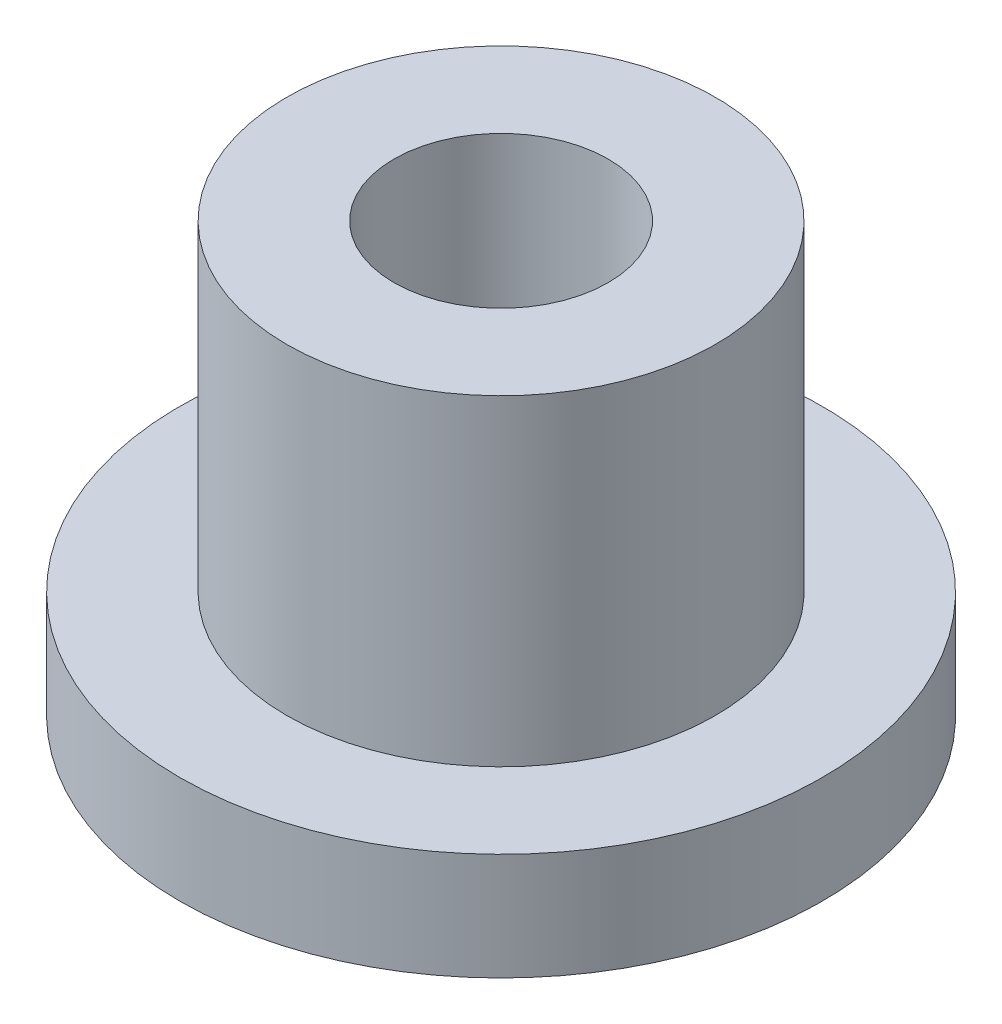
SolidWorks part; units mm, degrees
ref_plane "Front Plane" through (0, 0, 0) normal (0, 0, 1) x (1, 0, 0)
ref_plane "Top Plane" through (0, 0, 0) normal (0, 1, 0) x (1, 0, 0)
ref_plane "Right Plane" through (0, 0, 0) normal (1, 0, 0) x (0, 0, -1)
sketch "Sketch1" plane through (0, 0, 0) normal (0, 1, 0) x (1, 0, 0)
  circle A0 centre (0, 0) radius 6
  circle A1 centre (0, 0) radius 4
  circle A2 centre (0, 0) radius 2
  dimension "D1" = 12
  dimension "D2" = 8
  dimension "D3" = 4
extrude "Boss-Extrude1" add sketch "Sketch1" along normal blind 2 contours A0 A1 region at (-5.8303, 0, 0)
extrude "Boss-Extrude2" add sketch "Sketch1<3>" along normal blind 8 contours A1 A2 region at (-3.8869, 0, 0)
sketch "Sketch1<3>" plane through (0, 0, 0) normal (0, 1, 0) x (1, 0, 0) same geometry as "Sketch1"
